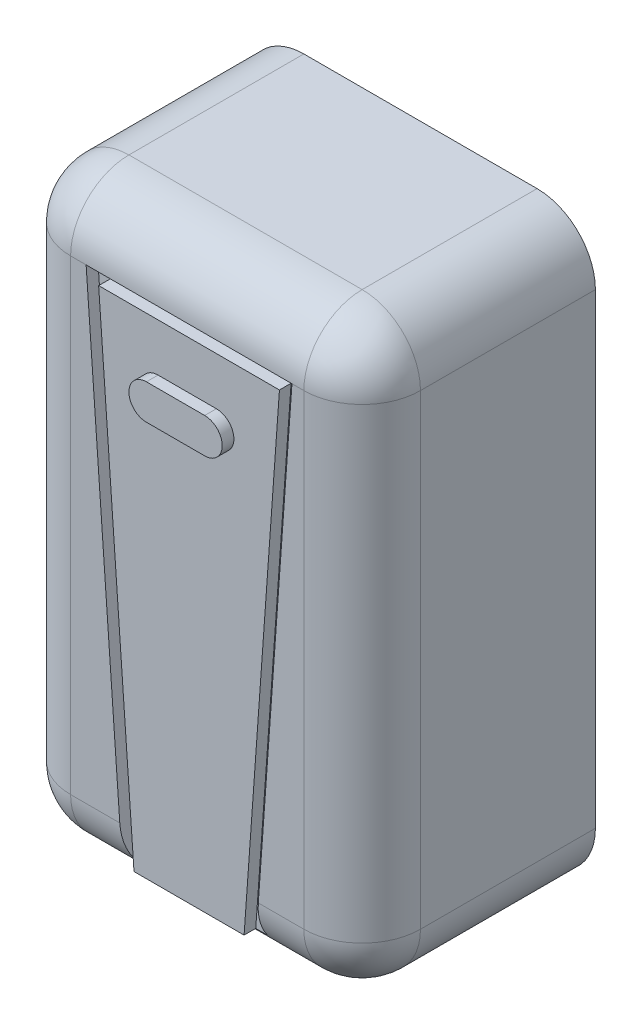
SolidWorks part; units mm, degrees
material "ABS"
ref_plane "Front Plane" through (0, 0, 0) normal (0, 0, 1) x (1, 0, 0)
ref_plane "Top Plane" through (0, 0, 0) normal (0, 1, 0) x (1, 0, 0)
ref_plane "Right Plane" through (0, 0, 0) normal (1, 0, 0) x (0, 0, -1)
sketch "Sketch1" plane through (0, 0, 0) normal (0, 0, 1) x (1, 0, 0)
  line L1 (0, 0) -> (76.2, 0)
  line L2 (0, 0) -> (0, 127)
  line L3 (0, 127) -> (76.2, 127)
  line L4 (76.2, 0) -> (76.2, 127)
  dimension "D1" = 127
  dimension "D2" = 76.2
extrude "Boss-Extrude1" add sketch "Sketch1" along normal blind 50.8
sketch "Sketch4" plane through (0, 0, 50.8) normal (0, 0, 1) x (1, 0, 0)
  line L0 (24.1459, 2.54) -> (52.8465, 2.54)
  line L1 (52.8465, 2.54) -> (60.9146, 114.3)
  line L2 (60.9146, 114.3) -> (16.0779, 114.3)
  line L3 (16.0779, 114.3) -> (24.1459, 2.54)
  line L4 (76.2, 127) -> (0, 127) construction
  line L5 (0, 0) -> (76.2, 0) construction
  point P6 (38.4962, 2.54)
  dimension "D1" = 12.7
  dimension "D2" = 2.54
extrude "Cut-Extrude1" cut sketch "Sketch4" against normal blind 2.54 contours L3 L0 L1 L2
sketch "Sketch5" plane through (0, 0, 48.26) normal (0, 0, 1) x (1, 0, 0)
  line L8 (58.1846, 111.76) -> (18.8079, 111.76)
  line L9 (18.8079, 111.76) -> (26.5092, 5.08)
  line L10 (26.5092, 5.08) -> (50.4833, 5.08)
  line L11 (50.4833, 5.08) -> (58.1846, 111.76)
  line L12 (58.1846, 111.76) -> (18.8079, 111.76)
  line L13 (18.8079, 111.76) -> (26.5092, 5.08)
  line L14 (26.5092, 5.08) -> (50.4833, 5.08)
  line L15 (50.4833, 5.08) -> (58.1846, 111.76)
  dimension "D1" = 2.54
extrude "Boss-Extrude2" add sketch "Sketch5" along normal blind 2.54
fillet "Fillet2" radius 12.7 8 edges at (0, 63.5, 50.8) (0, 0, 25.4) (38.1, 0, 50.8) (76.2, 0, 25.4) (76.2, 63.5, 50.8) (76.2, 127, 25.4) (38.1, 127, 50.8) (0, 127, 25.4)
sketch "Sketch6" plane through (0, 0, 50.8) normal (0, 0, 1) x (1, 0, 0)
  line L0 (31.75, 97.5399) -> (44.45, 97.5399) construction
  line L1 (31.75, 101.3499) -> (44.45, 101.3499)
  line L2 (31.75, 93.7299) -> (44.45, 93.7299)
  line L3 (0, 12.7) -> (0, 114.3) construction
  arc A0 (31.75, 101.3499) -> (31.75, 93.7299) centre (31.75, 97.5399) ccw
  arc A1 (44.45, 93.7299) -> (44.45, 101.3499) centre (44.45, 97.5399) ccw
  point P2 (38.1, 97.5399)
  dimension "D1" = 7.62
  dimension "D2" = 12.7
  dimension "D3" = 38.1
extrude "Cut-Extrude2" cut sketch "Sketch6" against normal blind 2.54
sketch "Sketch7" plane through (0, 0, 50.8) normal (0, 0, 1) x (1, 0, 0)
  line L8 (31.75, 93.7299) -> (44.45, 93.7299)
  line L9 (44.45, 101.3499) -> (31.75, 101.3499)
  line L10 (31.75, 93.7299) -> (44.45, 93.7299)
  line L11 (44.45, 101.3499) -> (31.75, 101.3499)
  arc A6 (44.45, 93.7299) -> (44.45, 101.3499) centre (44.45, 97.5399) ccw
  arc A7 (31.75, 101.3499) -> (31.75, 93.7299) centre (31.75, 97.5399) ccw
  arc A8 (44.45, 93.7299) -> (44.45, 101.3499) centre (44.45, 97.5399) ccw
  arc A9 (31.75, 101.3499) -> (31.75, 93.7299) centre (31.75, 97.5399) ccw
  dimension "D1" = 0
extrude "Boss-Extrude3" add sketch "Sketch7" along normal blind 2.54 separate body
ref_plane "Back Plane" through (0, 0, 0) normal (0, 0, -1) x (-1, 0, 0)
shell "Shell1" thickness 2.54 removed face at (38.1, 63.5, 0)
sketch "Sketch8" plane through (0, 0, 0) normal (0, 0, -1) x (-1, 0, 0)
  line L30 (-73.66, 114.3) -> (-73.66, 12.7)
  line L31 (-63.5, 2.54) -> (-12.7, 2.54)
  line L32 (-2.54, 12.7) -> (-2.54, 114.3)
  line L33 (-12.7, 124.46) -> (-63.5, 124.46)
  line L34 (-73.66, 114.3) -> (-73.66, 12.7)
  line L35 (-63.5, 2.54) -> (-12.7, 2.54)
  line L36 (-2.54, 12.7) -> (-2.54, 114.3)
  line L37 (-12.7, 124.46) -> (-63.5, 124.46)
  arc A28 (-73.66, 12.7) -> (-63.5, 2.54) centre (-63.5, 12.7) ccw
  arc A29 (-12.7, 2.54) -> (-2.54, 12.7) centre (-12.7, 12.7) ccw
  arc A30 (-2.54, 114.3) -> (-12.7, 124.46) centre (-12.7, 114.3) ccw
  arc A31 (-63.5, 124.46) -> (-73.66, 114.3) centre (-63.5, 114.3) ccw
  arc A32 (-73.66, 12.7) -> (-63.5, 2.54) centre (-63.5, 12.7) ccw
  arc A33 (-12.7, 2.54) -> (-2.54, 12.7) centre (-12.7, 12.7) ccw
  arc A34 (-2.54, 114.3) -> (-12.7, 124.46) centre (-12.7, 114.3) ccw
  arc A35 (-63.5, 124.46) -> (-73.66, 114.3) centre (-63.5, 114.3) ccw
  dimension "D2" = 2.54
extrude "Boss-Extrude4" add sketch "Sketch8" against normal blind 2.54
